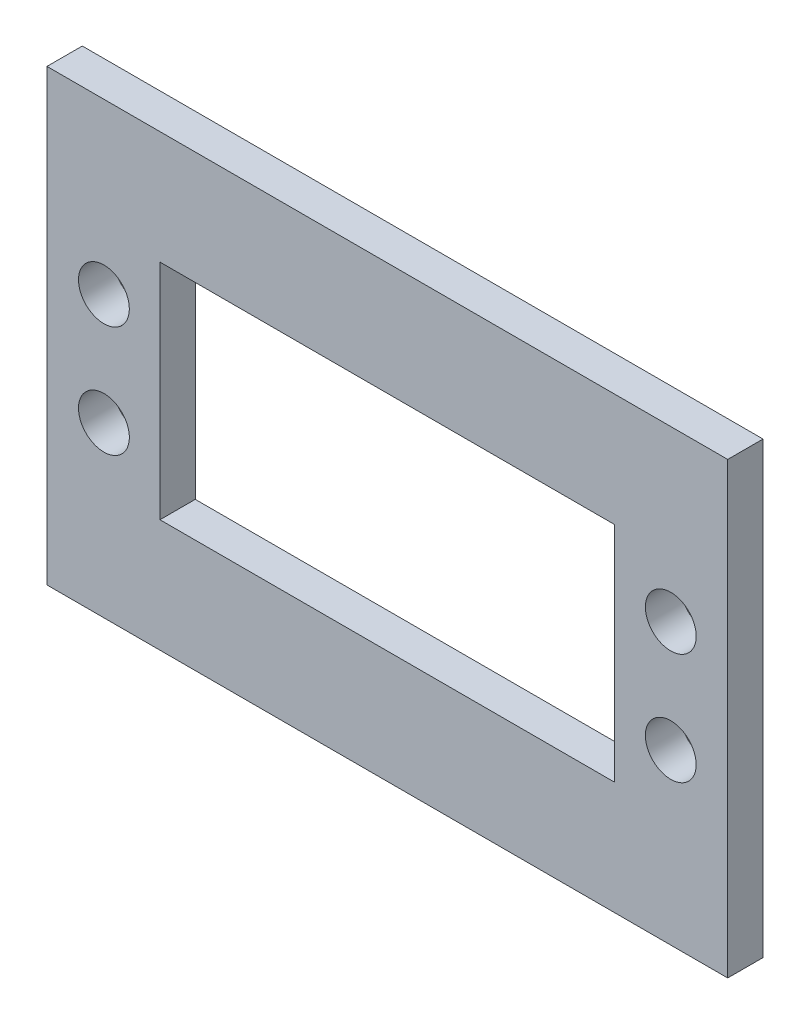
SolidWorks part; units mm, degrees
ref_plane "Front" through (0, 0, 0) normal (0, 0, 1) x (1, 0, 0)
ref_plane "Top" through (0, 0, 0) normal (0, 1, 0) x (1, 0, 0)
ref_plane "Right" through (0, 0, 0) normal (1, 0, 0) x (0, 0, -1)
sketch "Sketch1" plane through (0, 0, 0) normal (0, 0, 1) x (1, 0, 0)
  line L0 (-10.16, -10.16) -> (-10.16, 30.226)
  line L1 (0, 0) -> (40.894, 0)
  line L2 (0, 0) -> (0, 20.066)
  line L3 (0, 20.066) -> (40.894, 20.066)
  line L4 (40.894, 0) -> (40.894, 20.066)
  line L5 (-10.16, 30.226) -> (51.054, 30.226)
  line L6 (51.054, -10.16) -> (51.054, 30.226)
  line L7 (-10.16, -10.16) -> (51.054, -10.16)
  dimension "D1" = 40.894
  dimension "D2" = 20.066
  dimension "D3" = 10.16
extrude "Boss-Extrude1" add sketch "Sketch1" along normal blind 3.175
sketch "Sketch2" plane through (0, 0, 3.175) normal (0, 0, 1) x (1, 0, 0)
  line L0 (20.447, 30.226) -> (20.447, -10.16) construction
  line L1 (51.054, 30.226) -> (-10.16, 30.226) construction
  line L2 (-10.16, -10.16) -> (51.054, -10.16) construction
  line L3 (-10.16, 10.033) -> (51.054, 10.033) construction
  line L4 (-10.16, 30.226) -> (-10.16, -10.16) construction
  line L5 (51.054, -10.16) -> (51.054, 30.226) construction
  line L6 (0, 20.066) -> (0, 0) construction
  circle A0 centre (-5.04, 15.033) radius 2.286
  circle A1 centre (-5.04, 5.033) radius 2.286
  circle A2 centre (45.934, 5.033) radius 2.286
  circle A3 centre (45.934, 15.033) radius 2.286
  point P16 (0, 0)
  point P17 (0, 0)
  dimension "D1" = 4.572
  dimension "D2" = 5.04
  dimension "D3" = 5
extrude "Cut-Extrude1" cut sketch "Sketch2" against normal through all
